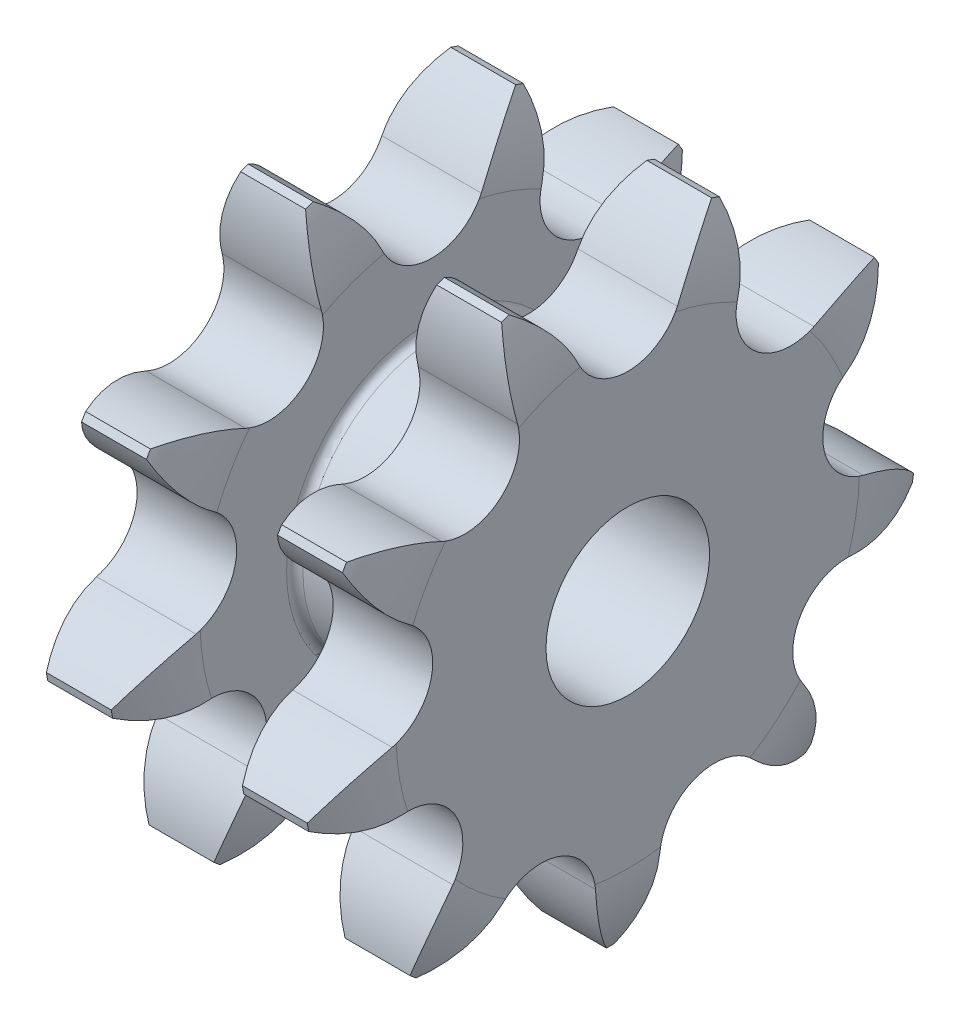
SolidWorks part; units mm, degrees
ref_plane "Plane1" through (0, 0, 0) normal (0, 0, 1) x (1, 0, 0)
ref_plane "Plane2" through (0, 0, 0) normal (0, 1, 0) x (1, 0, 0)
ref_plane "Plane3" through (0, 0, 0) normal (1, 0, 0) x (0, 0, -1)
sketch "Clipboard" plane through (0, 0, 0) normal (0, 1, 0) x (1, 0, 0)
  line L0 (0, 0) -> (12.5436, -1.9867)
  line L1 (-15, 0) -> (100, 0) construction
  line L2 (0, 0) -> (-0.8416, 0.9512)
  line L3 (0, 0) -> (-11.863, 4.5341)
  line L4 (0, 0) -> (3.0618, 0.4849)
  line L5 (0, 0) -> (-2.8109, -1.0484)
  line L6 (0, 0) -> (-17.9719, -12.1257)
  line L7 (-0.8416, 0.9512) -> (22.6002, 5.5078)
  line L8 (-76.2, 38.1) -> (-75.2, 38.1)
  line L9 (-73.4321, 41.7084) -> (-72.837, 41.7846)
  line L10 (-73.4741, 12.9512) -> (-59.0941, 12.9512)
  circle A0 centre (0, 0) radius 3.975
  circle A1 centre (0, 0) radius 10.0465
  circle A2 centre (0, 0) radius 25
  dimension "Num_teeth" = 9
  dimension "Thickness" = 21.68
  dimension "Fillet_rad" = 0.6
sketch "BasProSke" plane through (0, 0, 0) normal (0, 1, 0) x (1, 0, 0)
  line L0 (-10, 0) -> (60, 0) construction
  line L1 (0, 0) -> (0, 16.9929)
  line L2 (0, 0) -> (21.68, 0)
  line L3 (21.68, 0) -> (21.68, 16.9929)
  line L4 (20.41, 22.5287) -> (1.27, 22.5287)
  arc A0 (0, 16.9929) -> (1.27, 22.5287) centre (12.7, 16.9929) cw
  arc A1 (21.68, 16.9929) -> (20.41, 22.5287) centre (8.98, 16.9929) ccw
  dimension "D1" = 12.7
  dimension "Thickness" = 21.68
  dimension "Diameter" = 45.0573
  dimension "G1" = 1.27
revolve "Base-Revolve" add sketch "BasProSke" angle 360 about L0
sketch "GrvSke" plane through (0, 0, 0) normal (0, 1, 0) x (1, 0, 0)
  line L0 (7.3, 16.9929) -> (7.3, 10.6465)
  line L1 (7.9, 10.0465) -> (13.78, 10.0465)
  line L2 (14.38, 10.6465) -> (14.38, 16.9929)
  line L3 (6.03, 22.5287) -> (15.65, 22.5287)
  line L4 (10.84, 0) -> (10.84, 52.07) construction
  line L5 (-10, 0) -> (60, 0) construction
  line L6 (0, 0) -> (35.56, 0) construction
  arc A0 (14.38, 16.9929) -> (15.65, 22.5287) centre (27.08, 16.9929) cw
  arc A1 (7.3, 16.9929) -> (6.03, 22.5287) centre (-5.4, 16.9929) ccw
  arc A2 (7.3, 10.6465) -> (7.9, 10.0465) centre (7.9, 10.6465) ccw
  arc A3 (13.78, 10.0465) -> (14.38, 10.6465) centre (13.78, 10.6465) ccw
  dimension "D1" = 12.7
  dimension "Diameter" = 45.0573
  dimension "Fillet_rad" = 0.6
  dimension "G1" = 1.27
  dimension "Grv_width" = 7.08
revolve "Groove" cut sketch "GrvSke" angle 360 about L6
sketch "TooCutSke" plane through (0, 0, 0) normal (1, 0, 0) x (0, 0, -1)
  line L0 (0, 18.6059) -> (3.6386, 16.9092) construction
  line L1 (0, 0) -> (0, 107) construction
  line L2 (0, 18.6059) -> (-10, 18.6059) construction
  line L3 (0, 18.6059) -> (-3.6386, 16.9092) construction
  arc A0 (3.6386, 16.9092) -> (7.9748, 21.6037) centre (13.1494, 12.4742) cw
  arc A1 (3.6386, 16.9092) -> (-3.6386, 16.9092) centre (0, 18.6059) cw
  arc A2 (-3.6386, 16.9092) -> (-7.9748, 21.6037) centre (-13.1494, 12.4742) ccw
  arc A3 (7.9748, 21.6037) -> (-7.9748, 21.6037) centre (0, 0) ccw
extrude "ToothCut" cut sketch "TooCutSke" along normal through all
pattern_circular "TeethCuts" count 9 every 40 about axis through (-10, 0, 0) along (1, 0, 0) of "ToothCut"
sketch "HubNeaOneSke" plane through (0, 0, 0) normal (-1, 0, 0) x (0, 0, 1)
  circle A0 centre (0, 0) radius 10.0465
  dimension "Diameter" = 20.093
extrude "HubNearOne" [suppressed] add sketch "HubNeaOneSke" along normal blind 2.2005
fillet "HubNearOneFillet" [suppressed] radius 0.6
sketch "HubNeaBotSke" plane through (0, 0, 0) normal (-1, 0, 0) x (0, 0, 1)
  circle A0 centre (0, 0) radius 10.0465
  dimension "Diameter" = 20.093
extrude "HubNearBoth" [suppressed] add sketch "HubNeaBotSke" along normal blind 1.1003
fillet "HubNearBothFillet" [suppressed] radius 0.6
ref_plane "FarPln" through (21.68, 0, 0) normal (1, 0, 0) x (0, 0, -1)
sketch "HubFarSke" plane through (21.68, 0, 0) normal (1, 0, 0) x (0, 0, -1)
  circle A0 centre (0, 0) radius 10.0465
  dimension "Diameter" = 20.093
extrude "HubFar" [suppressed] add sketch "HubFarSke" along normal blind 1.1003
fillet "HubFarFillet" [suppressed] radius 0.6
sketch "BorSke" plane through (0, 0, 0) normal (1, 0, 0) x (0, 0, -1)
  circle A0 centre (0, 0) radius 6
  dimension "Diameter" = 12
extrude "Bore" cut sketch "BorSke" along normal mid plane 47.761
sketch "KeySke" plane through (0, 0, 0) normal (1, 0, 0) x (0, 0, -1)
  line L0 (-1, 0) -> (-1, 7)
  line L1 (-1, 7) -> (1, 7)
  line L2 (1, 7) -> (1, 0)
  line L3 (0, 0) -> (0, 34) construction
  line L4 (-1, 0) -> (1, 0)
  dimension "Offset" = 7
  dimension "Width" = 2
extrude "Keyway" [suppressed] cut sketch "KeySke" along normal mid plane 47.761
pattern_circular "Keyway2" [suppressed] count 2 every 90 about axis through (-10, 0, 0) along (1, 0, 0) reverse direction yes
equation "' \"Pitch@Clipboard\" = 12.7"
equation "' \"Num_strands@Clipboard\" = 2"
equation "' \"Num_teeth@Clipboard\" = 9"
equation "' \"Hub_dia@Clipboard\" = 50"
equation "' \"Overall_len@Clipboard\" = 3"
equation "' \"Diameter@BorSke\" = 12"
equation "' \"T_dim@Clipboard\" = 1"
equation "' \"Width@KeySke\" = 2"
equation "' \"Dr@Clipboard\" = 7.95"
equation "' \"Face_width@Clipboard\" = 7.3"
equation "' \"Side_radius@Clipboard\" = 12.7"
equation "' \"Side_relief@Clipboard\" = 1.27"
equation "' \"Transv_pitch@Clipboard\" = 14.38"
equation "' \"Show_teeth@Clipboard\" = 9"
equation "' \"Fillet_rad@Clipboard\" = 0.6"
equation "' \"Plate_wid@Clipboard\" = 12"
equation "\"Num_teeth@Clipboard\" = int( \"Num_teeth@Clipboard\" )"
equation "\"Num_teeth@Clipboard\" = ((sgn( \"Num_teeth@Clipboard\" - 5.0)+1)*( \"Num_teeth@Clipboard\" - 5.0))/2 +5.0"
equation "\"Num_teeth@Clipboard\" = ((sgn( \"Num_teeth@Clipboard\" - 200.0)-1)*( \"Num_teeth@Clipboard\" - 200.0))/-2 +200.0"
equation "\"MHD@Clipboard\" = \"Pitch@Clipboard\" * (1.0 / tan(3.14159265 / \"Num_teeth@Clipboard\" )) - 1.05 * \"Plate_wid@Clipboard\" - 2.0 * \"Fillet_rad@Clipboard\" - 1.0"
equation "\"Thickness@Clipboard\"  = \"Face_width@Clipboard\" + (\"Num_strands@Clipboard\" - 1) * \"Transv_pitch@Clipboard\""
equation "\"OAL@Clipboard\" = \"Thickness@Clipboard\" + 2 * \"Fillet_rad@Clipboard\" + 1"
equation "\"MHD@Clipboard\" = ((sgn( \"MHD@Clipboard\" - \"Hub_dia@Clipboard\" )-1)*( \"MHD@Clipboard\" - \"Hub_dia@Clipboard\" ))/-2+ \"Hub_dia@Clipboard\""
equation "\"OAL@Clipboard\" = ((sgn( \"OAL@Clipboard\" - \"Overall_len@Clipboard\" )+1)*( \"OAL@Clipboard\" - \"Overall_len@Clipboard\" ))/2 + \"Overall_len@Clipboard\" + 0.0005"
equation "\"Num_teeth@TeethCuts\" = int( \"Show_teeth@Clipboard\" ) + 1"
equation "\"Num_teeth@TeethCuts\" = ((sgn( \"Num_teeth@TeethCuts\" - \"Num_teeth@Clipboard\" )-1)*( \"Num_teeth@TeethCuts\" - \"Num_teeth@Clipboard\" ))/-2+ \"Num_teeth@Clipboard\""
equation "\"Num_teeth@TeethCuts\" = ((sgn( \"Num_teeth@TeethCuts\" - 2.0)+1)*( \"Num_teeth@TeethCuts\" - 2.0))/2 +2.0"
equation "\"Angle@TeethCuts\" = 360.0 / \"Num_teeth@Clipboard\""
equation "\"Seat_radius@TooCutSke\" = ( \"Pitch@Clipboard\" / 2.0) / sin(3.14159265 / \"Num_teeth@Clipboard\" ) - \"Dr@Clipboard\" / 2.0 + \"Dr@Clipboard\" * 0.505"
equation "\"R1@TooCutSke\"  = \"Dr@Clipboard\" * 0.505"
equation "\"X@TooCutSke\" = 140.0 - (90.0 / \"Num_teeth@Clipboard\")"
equation "\"R2@TooCutSke\" = 0.12 * \"Dr@Clipboard\" * ( \"Num_teeth@Clipboard\" + 2.0)"
equation "\"Overcut@TooCutSke\" = 0.5 + 0.625 * \"Pitch@Clipboard\" - 0.5 * \"Dr@Clipboard\"  +  \"Pitch@Clipboard\" / 2.0 / sin(3.14159265 / \"Num_teeth@Clipboard\" )"
equation "\"Diameter@BasProSke\" = 2.0 * ( 0.625 * \"Pitch@Clipboard\" - 0.5 * \"Dr@Clipboard\"  +  \"Pitch@Clipboard\" / 2.0 / sin(3.14159265 / \"Num_teeth@Clipboard\" ))"
equation "\"Thickness@BasProSke\"  = \"Thickness@Clipboard\""
equation "\"G1@BasProSke\" =  \"Side_relief@Clipboard\""
equation "\"G2@BasProSke\" =  \"Side_relief@Clipboard\""
equation "\"D1@BasProSke\" =  \"Side_radius@Clipboard\""
equation "\"Diameter@GrvSke\" = \"Diameter@BasProSke\""
equation "\"G1@GrvSke\" = \"Side_relief@Clipboard\""
equation "\"D1@GrvSke\" = \"Side_radius@Clipboard\""
equation "\"Grv_diam@GrvSke\" =  \"Pitch@Clipboard\" * (1.0 / tan(3.14159265 / \"Num_teeth@Clipboard\" ))- 1.05 * \"Plate_wid@Clipboard\" - 2.0 * \"Fillet_rad@Clipboard\" - 1.0"
equation "\"Grv_width@GrvSke\" =  \"Transv_pitch@Clipboard\" - \"Face_width@Clipboard\""
equation "\"Offset@GrvSke\" = \"Grv_width@GrvSke\" / 2.0 + \"Face_width@Clipboard\""
equation "\"Fillet_rad@GrvSke\" = \"Fillet_rad@Clipboard\""
equation "\"Diameter@HubNeaOneSke\" = \"MHD@Clipboard\""
equation "\"Length@HubNearOne\" = \"OAL@Clipboard\" - \"Thickness@BasProSke\""
equation "\"Diameter@HubNeaBotSke\" = \"MHD@Clipboard\""
equation "\"Length@HubNearBoth\" = ( \"OAL@Clipboard\" - \"Thickness@BasProSke\" ) / 2.0"
equation "\"D1@HubNearOneFillet\" = \"Fillet_rad@Clipboard\""
equation "\"D1@HubNearBothFillet\" = \"Fillet_rad@Clipboard\""
equation "\"Thickness@FarPln\" = \"Thickness@BasProSke\""
equation "\"Diameter@HubFarSke\" = \"MHD@Clipboard\""
equation "\"Length@HubFar\" = ( \"OAL@Clipboard\" - \"Thickness@BasProSke\" ) / 2.0"
equation "\"D1@HubFarFillet\" = \"Fillet_rad@Clipboard\""
equation "\"D1@Bore\" = \"OAL@Clipboard\" * 2.0"
equation "\"D1@Keyway\" = \"OAL@Clipboard\" * 2.0"
equation "\"Offset@KeySke\" = \"T_dim@Clipboard\" + \"Diameter@BorSke\" / 2.0"
